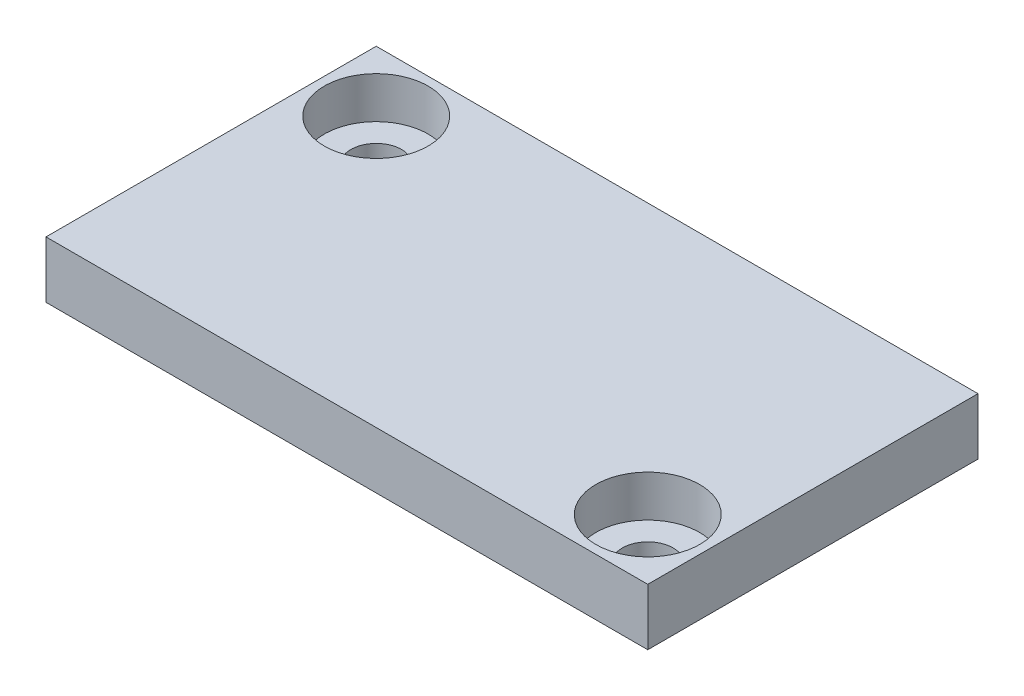
SolidWorks part; units mm, degrees
ref_plane "Front Plane" through (0, 0, 0) normal (0, 0, 1) x (1, 0, 0)
ref_plane "Top Plane" through (0, 0, 0) normal (0, 1, 0) x (1, 0, 0)
ref_plane "Right Plane" through (0, 0, 0) normal (1, 0, 0) x (0, 0, -1)
sketch "Sketch1" plane through (0, 0, 0) normal (0, 1, 0) x (1, 0, 0)
  line L1 (-20.2205, 11.0966) -> (20.2205, 11.0966)
  line L2 (-20.2205, 11.0966) -> (-20.2205, -11.0966)
  line L3 (-20.2205, -11.0966) -> (20.2205, -11.0966)
  line L4 (20.2205, 11.0966) -> (20.2205, -11.0966)
  line L5 (-20.2205, 11.0966) -> (20.2205, -11.0966) construction
  line L6 (-20.2205, -11.0966) -> (20.2205, 11.0966) construction
  point P0 (0, 0)
  dimension "D1" = 40.4409
  dimension "D2" = 22.1932
extrude "Boss-Extrude1" add sketch "Sketch1" along normal blind 3.81
sketch "Sketch3" plane through (0, 3.81, 0) normal (0, 1, 0) x (1, 0, 0)
  line L0 (-12.0925, 7.0326) -> (-20.2205, 7.0326) construction
  line L1 (-20.2205, 11.0966) -> (-12.0925, 11.0966)
  line L2 (-20.2205, 11.0966) -> (-20.2205, 2.9686)
  line L3 (-20.2205, 2.9686) -> (-12.0925, 2.9686)
  line L4 (-12.0925, 11.0966) -> (-12.0925, 2.9686)
  line L5 (20.2205, -11.0966) -> (12.0925, -11.0966)
  line L6 (20.2205, -11.0966) -> (20.2205, -2.9686)
  line L7 (20.2205, -2.9686) -> (12.0925, -2.9686)
  line L8 (12.0925, -11.0966) -> (12.0925, -2.9686)
  line L9 (12.0925, -7.0326) -> (20.2205, -7.0326) construction
  circle A0 centre (-16.1565, 7.0326) radius 1.7018
  circle A1 centre (16.1565, -7.0326) radius 1.7018
  circle A2 centre (-16.1565, 7.0326) radius 3.4925
  circle A3 centre (16.1565, -7.0326) radius 3.4925
  dimension "D5" = 6.985
  dimension "D6" = 6.985
  dimension "D1" = 8.128
  dimension "D2" = 8.128
  dimension "D3" = 8.128
  dimension "D4" = 8.128
extrude "Cut-Extrude3" cut sketch "Sketch3" against normal blind 2.794 contours A2 | A3
extrude "Cut-Extrude4" cut sketch "Sketch3<4>" against normal through all contours A0 | A1
sketch "Sketch3<4>" plane through (0, 3.81, 0) normal (0, 1, 0) x (1, 0, 0) same geometry as "Sketch3"
